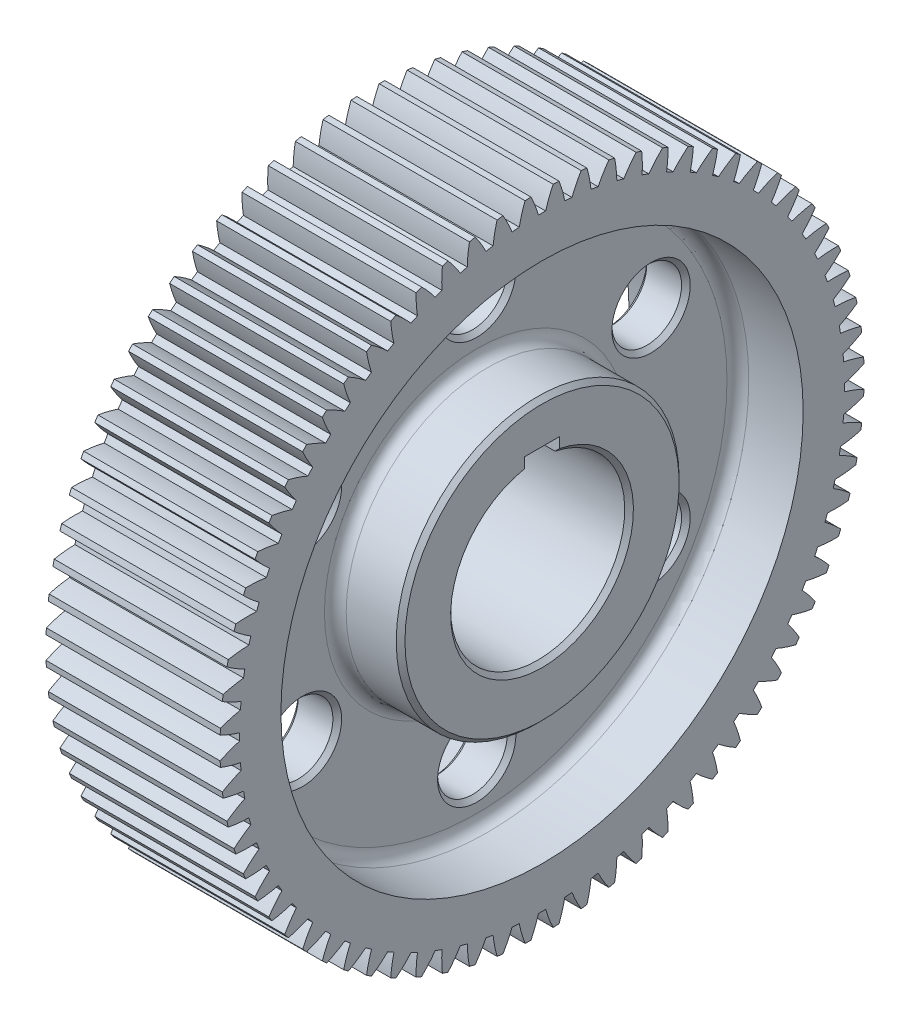
SolidWorks part; units mm, degrees
material "ASTM A36 Steel"
ref_plane "Plane1" through (0, 0, 0) normal (0, 0, 1) x (1, 0, 0)
ref_plane "Plane2" through (0, 0, 0) normal (0, 1, 0) x (1, 0, 0)
ref_plane "Plane3" through (0, 0, 0) normal (1, 0, 0) x (0, 0, -1)
other "Configuration Table"
sketch "HoldingSke" plane through (0, 0, 0) normal (0, 1, 0) x (1, 0, 0)
  line L0 (0, 0) -> (0.0773, -0.2378)
  line L1 (-15, 0) -> (100, 0) construction
  line L2 (0, 0) -> (-2.1039, 2.3779)
  line L3 (0, 0) -> (-11.863, 4.5341)
  line L4 (0, 0) -> (2.6687, 8.2133)
  line L5 (0, 0) -> (-46.8476, -17.4728)
  line L6 (0, 0) -> (-66.317, -44.7443)
  line L7 (-2.1039, 2.3779) -> (15.1161, 80.5027)
  line L8 (-76.2, 54.61) -> (-70.8, 54.61)
  line L9 (-71.009, 38.7566) -> (-53.1078, 45.2721)
  line L10 (-76.2, 71.12) -> (104.1128, 71.12)
  line L11 (0, 0) -> (-80, 0)
  line L12 (-76.2, 101.6) -> (-76.073, 101.6)
  line L13 (24.9733, 27.94) -> (52.9518, 28.4284)
  line L14 (24.9733, 27.94) -> (24.9743, 27.94)
  line L15 (24.9733, 27.94) -> (100.4006, 29.5858)
  line L16 (-63.627, -4) -> (-12.827, -4)
  circle A0 centre (0, 0) radius 40
  circle A1 centre (0, 0) radius 37.5
  circle A2 centre (0, 0) radius 37.5
  circle A3 centre (0, 0) radius 40
  dimension "MHD" = 75
  dimension "Hub_dia" = 75
  dimension "Bore" = 80
  dimension "MBD" = 80
  dimension "Num_teeth" = 72
  dimension "Pitch_radius" = 180.3128
  dimension "Pitch" = 0.25
  dimension "Width" = 80
  dimension "Overall_len" = 50
  dimension "Show_teeth" = 72
  dimension "Thickness" = 80
  dimension "OAL" = 80.0001
  dimension "T_dim" = 5.4
  dimension "Ap" = 20
  dimension "H" = 19.05
  dimension "Backlash" = 0.127
  dimension "Addendum_fac" = 1
  dimension "Dedendum_fac" = 1.25
  dimension "Clearance_fac" = 0.25
  dimension "Dedendum_add" = 0.001
  dimension "Module" = 4
sketch "BasProSke" plane through (0, 0, 0) normal (0, 1, 0) x (1, 0, 0)
  line L0 (-10, 0) -> (60, 0) construction
  line L1 (0, 0) -> (0, 148)
  line L2 (0, 0) -> (80, 0)
  line L3 (80, 0) -> (80, 148)
  line L4 (80, 148) -> (0, 148)
  dimension "Diameter" = 296
  dimension "Thickness" = 80
revolve "Base-Revolve" add sketch "BasProSke" angle 360 about L0
sketch "TooCutSke" plane through (0, 0, 0) normal (1, 0, 0) x (0, 0, -1)
  line L1 (0, 0) -> (0, 107) construction
  line L2 (0, 0) -> (-3.3636, 143.9607) construction
  line L3 (0, 0) -> (-12.5598, 287.6668) construction
  line L4 (-3.3636, 143.9607) -> (-6.2799, 143.8334) construction
  arc A0 (1.6538, 138.9892) -> (-1.6538, 138.9892) centre (0, 0) ccw
  arc A1 (5.1137, 147.937) -> (-5.1137, 147.937) centre (0, 0) ccw
  circle A2 centre (0, 0) radius 144 construction
  circle A3 centre (0, 0) radius 135.3157 construction
  arc A4 (-1.6538, 138.9892) -> (-5.1137, 147.937) centre (-56.9206, 122.7615) ccw
  arc A5 (5.1137, 147.937) -> (1.6538, 138.9892) centre (56.9206, 122.7615) ccw
  dimension "Root_dia" = 277.998
  dimension "Overcut_dia" = 296.0508
  dimension "Pitch_dia" = 288
  dimension "Base_dia" = 270.6315
  dimension "Flank_rad" = 57.6
  dimension "Half_ang" = 2.5
  dimension "Half_CT" = 2.9191
extrude "ToothCut" cut sketch "TooCutSke" along normal through all
fillet "Breaks" [suppressed] radius 0.08 tangent propagation no
fillet "RootFillets" [suppressed] radius 1.001
pattern_circular "TeethCuts" count 72 every 5 about axis through (-10, 0, 0) along (1, 0, 0) of "ToothCut", "RootFillets", "Breaks"
sketch "HubNeaOneSke" plane through (0, 0, 0) normal (-1, 0, 0) x (0, 0, 1)
  circle A0 centre (0, 0) radius 37.5
  dimension "Diameter" = 75
extrude "HubNearOne" [suppressed] add sketch "HubNeaOneSke" along normal blind 38.0001
sketch "HubNeaBotSke" plane through (0, 0, 0) normal (-1, 0, 0) x (0, 0, 1)
  circle A0 centre (0, 0) radius 37.5
  dimension "Diameter" = 75
extrude "HubNearBoth" [suppressed] add sketch "HubNeaBotSke" along normal blind 19
ref_plane "FarPln" through (80, 0, 0) normal (1, 0, 0) x (0, 0, -1)
sketch "HubFarSke" plane through (80, 0, 0) normal (1, 0, 0) x (0, 0, -1)
  circle A0 centre (0, 0) radius 37.5
  dimension "Diameter" = 75
extrude "HubFar" [suppressed] add sketch "HubFarSke" along normal blind 19
sketch "BorSke" plane through (0, 0, 0) normal (1, 0, 0) x (0, 0, -1)
  circle A0 centre (0, 0) radius 40
  dimension "Diameter" = 80
extrude "Bore" cut sketch "BorSke" along normal mid plane 160.0001
sketch "KeySke" plane through (0, 0, 0) normal (1, 0, 0) x (0, 0, -1)
  line L0 (-11, 0) -> (-11, 45.4)
  line L1 (-11, 45.4) -> (11, 45.4)
  line L2 (11, 45.4) -> (11, 0)
  line L3 (0, 0) -> (0, 34) construction
  line L4 (-11, 0) -> (11, 0)
  dimension "Offset" = 45.4
  dimension "Width" = 22
extrude "Keyway" [suppressed] cut sketch "KeySke" along normal mid plane 160.0001
pattern_circular "Keyway2" [suppressed] count 2 every 90 about axis through (-10, 0, 0) along (1, 0, 0)
sketch "Sketch1" plane through (80, 0, 0) normal (1, 0, 0) x (0, 0, -1)
  circle A0 centre (0, 0) radius 65
  circle A1 centre (0, 0) radius 120
  dimension "D1" = 130
  dimension "D2" = 240
extrude "Cut-Extrude1" cut sketch "Sketch1" against normal blind 30
extrude "Cut-Extrude2" cut sketch "Sketch1<2>" along normal blind 30 from surface starting at face at (0, 0, -40)
sketch "Sketch1<2>" plane through (80, 0, 0) normal (1, 0, 0) x (0, 0, -1) same geometry as "Sketch1"
sketch "Sketch2" plane through (80, 0, 0) normal (1, 0, 0) x (0, 0, -1)
  circle A0 centre (0, 0) radius 92.5
  circle A1 centre (0, 92.5) radius 16
  dimension "D1" = 32
  dimension "D2" = 185
extrude "Cut-Extrude3" cut sketch "Sketch2" against normal through all contours A0 A1 | A0 A1 region at (80, 85.4663, 0) region at (80, 99.0353, 0)
pattern_circular "CirPattern1" count 6 over 360 about axis through (50, 0, 0) along (1, 0, 0) of "Cut-Extrude3" reverse direction yes
sketch "Sketch3" plane through (80, 0, 0) normal (1, 0, 0) x (0, 0, -1)
  line L1 (-8, 34) -> (8, 34)
  line L2 (-8, 34) -> (-8, 46)
  line L3 (-8, 46) -> (8, 46)
  line L4 (8, 34) -> (8, 46)
  line L5 (-8, 34) -> (8, 46) construction
  line L6 (-8, 46) -> (8, 34) construction
  circle A0 centre (0, 0) radius 40 construction
  point P0 (0, 40)
  dimension "D1" = 16
  dimension "D2" = 12
extrude "Cut-Extrude4" cut sketch "Sketch3" against normal through all
fillet "Fillet1" radius 5 4 edges at (30, 0, -65) (30, 0, -120) (50, 0, -65) (50, 0, -120)
chamfer "Chamfer1" distance 2 angle 45 16 edges at (30, -46.25, 64.1073) (50, -46.25, 64.1073) (30, -92.5, -16) (50, -92.5, -16) (30, -46.25, -96.1073) (50, -46.25, -96.1073) (30, 46.25, -96.1073) (50, 46.25, -96.1073) (30, 92.5, -16) (50, 92.5, -16) (30, 46.25, 64.1073) (50, 46.25, 64.1073) (0, -40, 0) (0, 0, -65) (80, -40, 0) (80, 0, -65)
